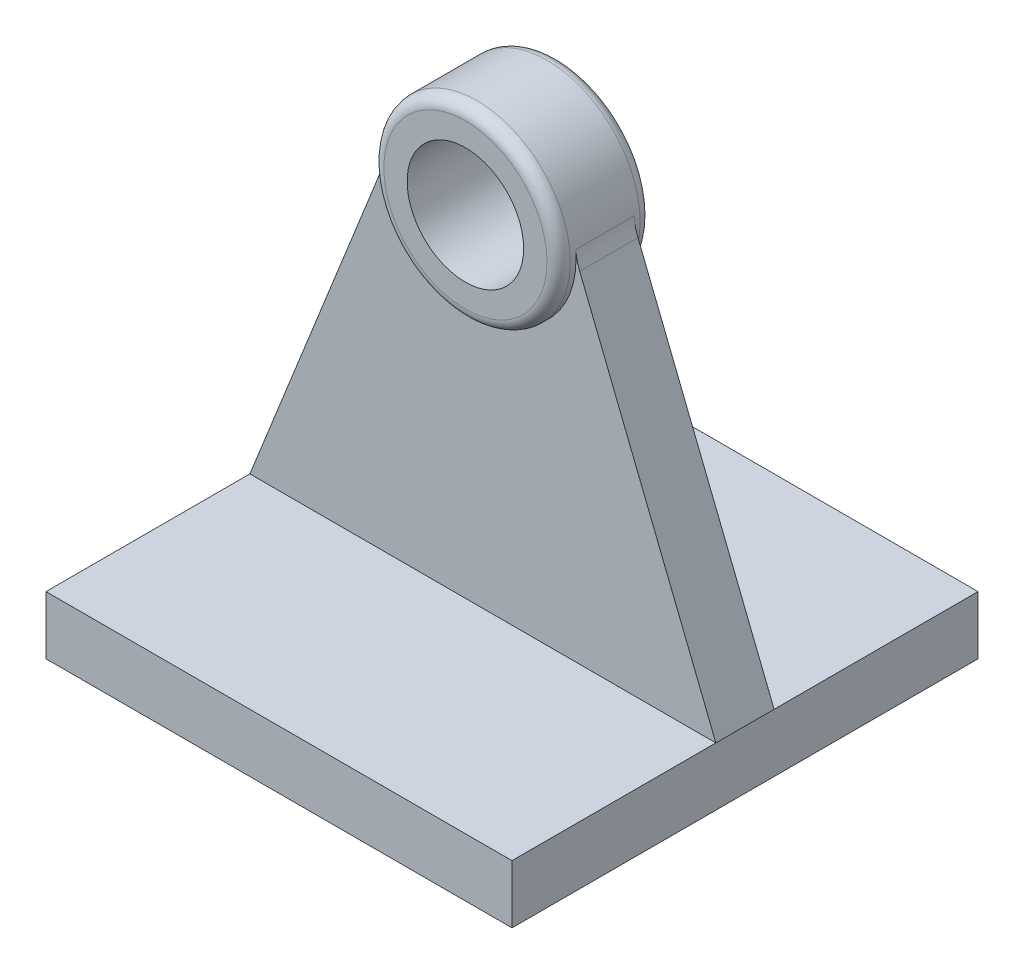
SolidWorks part; units mm, degrees
material "AISI 304"
ref_plane "Front Plane" through (0, 0, 0) normal (0, 0, 1) x (1, 0, 0)
ref_plane "Top Plane" through (0, 0, 0) normal (0, 1, 0) x (1, 0, 0)
ref_plane "Right Plane" through (0, 0, 0) normal (1, 0, 0) x (0, 0, -1)
sketch "Sketch1" plane through (0, 0, 0) normal (0, 1, 0) x (1, 0, 0)
  line L1 (-25.4, -25.4) -> (25.4, -25.4)
  line L2 (-25.4, -25.4) -> (-25.4, 25.4)
  line L3 (-25.4, 25.4) -> (25.4, 25.4)
  line L4 (25.4, -25.4) -> (25.4, 25.4)
  line L5 (-25.4, -25.4) -> (25.4, 25.4) construction
  line L6 (-25.4, 25.4) -> (25.4, -25.4) construction
  point P0 (0, 0)
  dimension "D1" = 50.8
  dimension "D2" = 50.8
extrude "Boss-Extrude1" add sketch "Sketch1" along normal blind 6.35
sketch "Sketch2" plane through (0, 0, 0) normal (0, 0, 1) x (1, 0, 0)
  line L0 (-25.4, 6.35) -> (25.4, 6.35) construction
  circle A0 centre (0, 44.45) radius 10.16
  circle A1 centre (0, 44.45) radius 6.35
  dimension "D1" = 38.1
extrude "Boss-Extrude2" add sketch "Sketch2" along normal mid plane 10.16 separate body
sketch "Sketch4" plane through (0, 0, 0) normal (0, 0, 1) x (1, 0, 0)
  line L0 (-10.16, 44.45) -> (-25.4, 6.35)
  line L1 (-25.4, 6.35) -> (25.4, 6.35) construction
  line L2 (-25.4, 6.35) -> (-25.4, 0) construction
  line L3 (-25.4, 6.35) -> (25.4, 6.35)
  line L4 (25.4, 6.35) -> (10.16, 44.45)
  circle A0 centre (0, 44.45) radius 10.16 construction
  arc A1 (-10.16, 44.45) -> (10.16, 44.45) centre (0, 44.45) ccw
extrude "Boss-Extrude3" add sketch "Sketch4" along normal mid plane 6.35
fillet "Fillet2" radius 1.27 2 edges at (10.16, 44.45, -5.08) (10.16, 44.45, 5.08)
fillet "Fillet3" radius 6.35 2 edges at (-10.16, 44.45, 0) (10.16, 44.45, 0)
